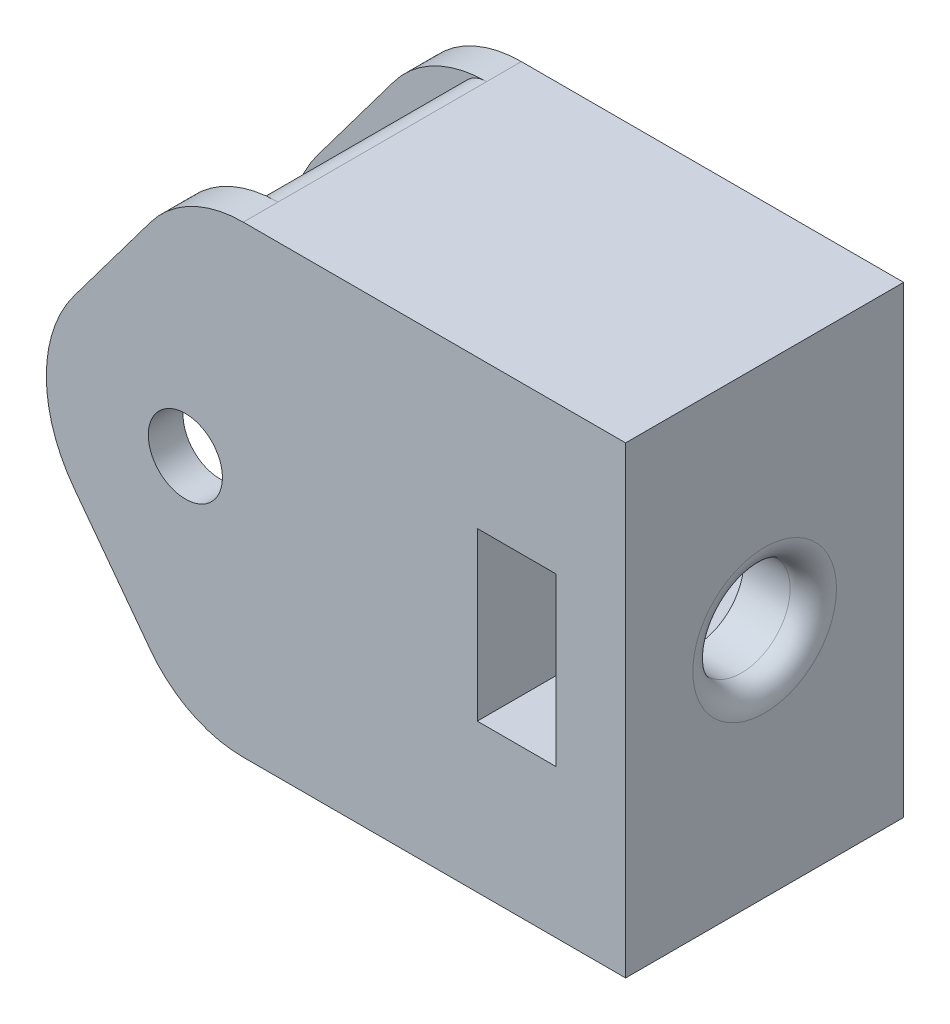
SolidWorks part; units mm, degrees
ref_plane "Спереди" through (0, 0, 0) normal (0, 0, 1) x (1, 0, 0)
ref_plane "Сверху" through (0, 0, 0) normal (0, 1, 0) x (1, 0, 0)
ref_plane "Справа" through (0, 0, 0) normal (1, 0, 0) x (0, 0, -1)
sketch "Эскиз1" plane through (0, 0, 0) normal (0, 0, 1) x (1, 0, 0)
  line L0 (-40.7301, 0) -> (24.5199, 0) construction
  line L1 (2.5, 10) -> (19, 10)
  line L2 (-10, 10) -> (24, 10) construction
  line L3 (-10, 10) -> (-10, -10) construction
  line L4 (-10, -10) -> (24, -10) construction
  line L5 (24, 10) -> (24, -10) construction
  line L6 (19, 10) -> (19, -10)
  line L7 (19, -10) -> (2.5, -10)
  line L8 (-1.5, 8) -> (-4.8, 3.6)
  line L9 (-1.5, -8) -> (-4.8, -3.6)
  line L10 (2.5, 5) -> (2.5, -5.7798) construction
  line L11 (12.6, 3.6) -> (16, 3.6)
  line L12 (12.6, 3.6) -> (12.6, -3.6)
  line L13 (12.6, -3.6) -> (16, -3.6)
  line L14 (16, 3.6) -> (16, -3.6)
  line L15 (12.6, 3.6) -> (16, -3.6) construction
  line L16 (12.6, -3.6) -> (16, 3.6) construction
  circle A0 centre (0, 0) radius 3 construction
  circle A1 centre (0, 0) radius 7 construction
  circle A3 centre (0, 0) radius 1.6
  arc A4 (-4.8, 3.6) -> (-4.8, -3.6) centre (0, 0) ccw
  arc A5 (-1.5, -8) -> (2.5, -10) centre (2.5, -5) ccw
  arc A6 (2.5, 10) -> (-1.5, 8) centre (2.5, 5) ccw
  arc A7 (2.5, 10) -> (2.1802, 7.6972) centre (2.5, 8.8264) ccw
  arc A8 (2.1802, -7.6972) -> (2.5, -10) centre (2.5, -8.8264) ccw
  arc A9 (2.1802, -7.6972) -> (2.1802, 7.6972) centre (0, 0) ccw
  point P9 (-10, 0)
  point P18 (14.3, 0)
  dimension "D4" = 6
  dimension "D5" = 14
  dimension "D7" = 3.2
  dimension "D8" = 12
  dimension "D13" = 10
  dimension "D14" = 10
  dimension "D1" = 20
  dimension "D2" = 34
  dimension "D3" = 10
  dimension "D9" = 5
  dimension "D10" = 3.4
  dimension "D11" = 7.2
  dimension "D12" = 3
extrude "Бобышка-Вытянуть1" add sketch "Эскиз1" along normal mid plane 12 contours A8 A9 A7 A6 L8 A4 L9 A5 A3 | A9 A8 L7 L6 L1 A7 L11 L14 L13 L12 region at (1.0957, 9.0214, 0) region at (11.7167, 0, 0)
extrude "Вырез-Вытянуть1" cut sketch "Эскиз1<3>" against normal mid plane 9 contours A8 A9 A7 A6 L8 A4 L9 A5 A3 region at (1.0957, 9.0214, 0)
sketch "Эскиз1<3>" plane through (0, 0, 0) normal (0, 0, 1) x (1, 0, 0) same geometry as "Эскиз1"
sketch "Эскиз2" plane through (19, 0, 0) normal (1, 0, 0) x (0, 0, -1)
  circle A0 centre (0, 0) radius 2.1
  dimension "D1" = 4.2
extrude "Вырез-Вытянуть2" cut sketch "Эскиз2" against normal through all
fillet "Скругление1" radius 1 2 edges at (7.9898, -0.4035, 2.0609) (19, 0, -2.1)
